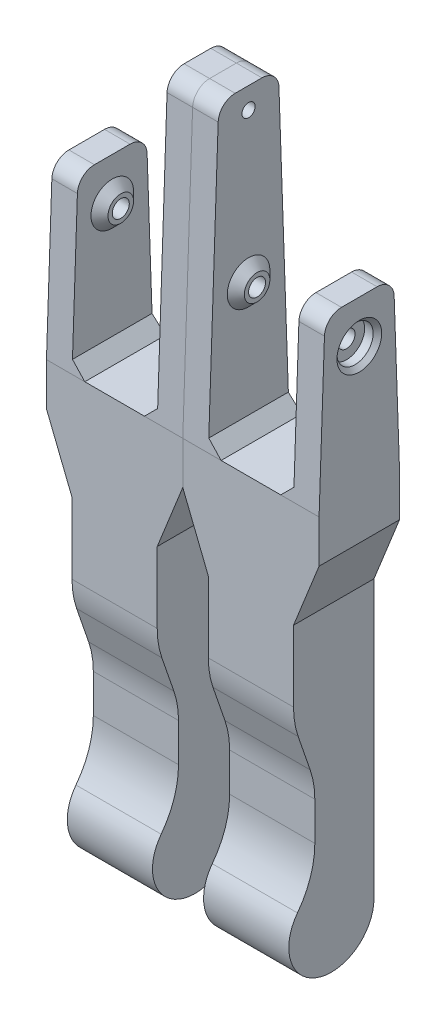
SolidWorks part; units mm, degrees
ref_plane "Front Plane" through (0, 0, 0) normal (0, 0, 1) x (1, 0, 0)
ref_plane "Top Plane" through (0, 0, 0) normal (0, 1, 0) x (1, 0, 0)
ref_plane "Right Plane" through (0, 0, 0) normal (1, 0, 0) x (0, 0, -1)
sketch "Sketch1" plane through (0, 0, 0) normal (1, 0, 0) x (0, 0, -1)
  line L0 (-9.4445, -30) -> (-7, 40)
  line L1 (-7, 40) -> (7, 40)
  line L2 (7, 40) -> (9.4445, -30)
  line L3 (9.4445, -30) -> (-9.4445, -30)
  circle A0 centre (0, 0) radius 2
  point P5 (0, -30)
  point P8 (0, 40)
  dimension "D1" = 4
  dimension "D2" = 40
  dimension "D3" = 92
  dimension "D4" = 30
  dimension "D5" = 14
extrude "Boss-Extrude1" add sketch "Sketch1" along normal blind 6
sketch "Sketch2" plane through (0, 0, 0) normal (-1, 0, 0) x (0, 0, 1)
  circle A0 centre (0, 0) radius 4.25
  dimension "D1" = 8.5
extrude "Cut-Extrude1" cut sketch "Sketch2" against normal blind 3
sketch "Sketch3" plane through (0, 0, 0) normal (-1, 0, 0) x (0, 0, 1)
  line L1 (-9.4445, -30) -> (9.4445, -30)
  line L2 (-9.4445, -30) -> (-9.4445, -40)
  line L3 (-9.4445, -40) -> (9.4445, -40)
  line L4 (9.4445, -30) -> (9.4445, -40)
  dimension "D1" = 10
extrude "Boss-Extrude2" add sketch "Sketch3" against normal blind 32
sketch "Sketch4" plane through (32, 0, 0) normal (1, 0, 0) x (0, 0, -1)
  line L0 (9.4445, -30) -> (-9.4445, -30)
  line L1 (-9.4445, -30) -> (-8.0476, 10)
  line L2 (-7, 40) -> (-9.4445, -30) construction
  line L3 (-8.0476, 10) -> (8.0476, 10)
  line L12 (9.4445, -30) -> (7, 40) construction
  line L13 (8.0476, 10) -> (9.4445, -30)
  circle A0 centre (0, 0) radius 2 construction
  circle A1 centre (0, 0) radius 2
  dimension "D1" = 10
extrude "Boss-Extrude3" add sketch "Sketch4" against normal blind 6
fillet "Fillet1" radius 4 4 edges at (3, 40, -7) (3, 40, 7) (29, 10, -8.0476) (29, 10, 8.0476)
extrude "Cut-Extrude2" cut sketch "Sketch2<2>" along normal blind 3 from surface starting at face at (32, -13.2632, 0)
sketch "Sketch2<2>" plane through (0, 0, 0) normal (-1, 0, 0) x (0, 0, 1) same geometry as "Sketch2"
chamfer "Chamfer1" distance 1 angle 45 2 edges at (0, 0, 4.25) (32, 0, 4.25)
chamfer "Chamfer2" distance 3 angle 45 2 edges at (6, -30, 0) (26, -30, 0)
sketch "Sketch5" plane through (6, 0, 0) normal (1, 0, 0) x (0, 0, -1)
  circle A0 centre (0, 0) radius 2 construction
  circle A1 centre (0, 0) radius 2
  circle A2 centre (0, 0) radius 3
  dimension "D1" = 1
extrude "Boss-Extrude4" add sketch "Sketch5" along normal blind 2
extrude "Boss-Extrude5" add sketch "Sketch5<2>" against normal blind 2 from surface starting at face at (26, 0, -2)
sketch "Sketch5<2>" plane through (6, 0, 0) normal (1, 0, 0) x (0, 0, -1) same geometry as "Sketch5"
chamfer "Chamfer4" distance 2 angle 45 2 edges at (26, 0, 3) (6, 0, 3)
sketch "Sketch7" plane through (0, 0, -9.4445) normal (0, 0, -1) x (-1, 0, 0)
  line L0 (-32, -40) -> (-26, -55)
  line L1 (-26, -55) -> (-26, -60)
  line L2 (-6, -60) -> (-6, -55)
  line L3 (-6, -55) -> (0, -40)
  line L4 (-6, -60) -> (-26, -60)
  line L5 (-32, -40) -> (0, -40) construction
  line L6 (-16, -60) -> (-16, -40) construction
  line L7 (0, -40) -> (-32, -40)
  dimension "D1" = 20
  dimension "D2" = 5
  dimension "D3" = 15
extrude "Boss-Extrude6" add sketch "Sketch7" against normal up to surface (18.8889 mm away) up to face at (16, -33.3333, 9.4445)
sketch "Sketch8" plane through (26, 0, 0) normal (1, 0, 0) x (0, 0, -1)
  line L1 (9.4445, -60) -> (-9.4445, -60)
  line L2 (-9.4445, -60) -> (-9.4445, -90)
  line L5 (9.4445, -60) -> (9.4445, -120)
  line L6 (-9.4445, -90) -> (-4.4445, -90)
  line L7 (-4.4445, -90) -> (-4.4445, -110.7872)
  arc A2 (-4.4445, -110.7872) -> (9.4445, -120) centre (-0.5555, -120) ccw
  point P10 (9.4445, -90)
  dimension "D1" = 60
  dimension "D2" = 5
  dimension "D3" = 20
extrude "Boss-Extrude7" add sketch "Sketch8" against normal up to surface (20 mm away) up to face at (6, -57.5, 0)
chamfer "Chamfer5" distance 15 angle 19 1 edges at (16, -90, 9.4445) first distance on face at (16, -49, 9.4445)
fillet "Fillet2" radius 20 3 edges at (16, -110.7872, 4.4445) (16, -89.5211, 4.4445) (16, -75, 9.4445)
sketch "Sketch9" plane through (6, 0, 0) normal (1, 0, 0) x (0, 0, -1)
  circle A0 centre (0, 35) radius 1.55
  dimension "D1" = 35
  dimension "D2" = 3.1
extrude "Cut-Extrude3" cut sketch "Sketch9" against normal up to surface (6 mm away) up to face at (0, 0, 5.25)
sketch "Sketch10" plane through (0, 0, 0) normal (-1, 0, 0) x (0, 0, 1)
  circle A0 centre (0, 35) radius 1.55 construction
  circle A1 centre (0, 35) radius 1.55
  circle A2 centre (0, 35) radius 3.25
  dimension "D1" = 6.5
extrude "Cut-Extrude4" cut sketch "Sketch10" against normal blind 3
chamfer "Chamfer6" distance 1 angle 45 1 edges at (0, 35, 3.25)
mirror "Mirror1" about plane through (0, 0, 0) normal (1, 0, 0) of bodies 111
